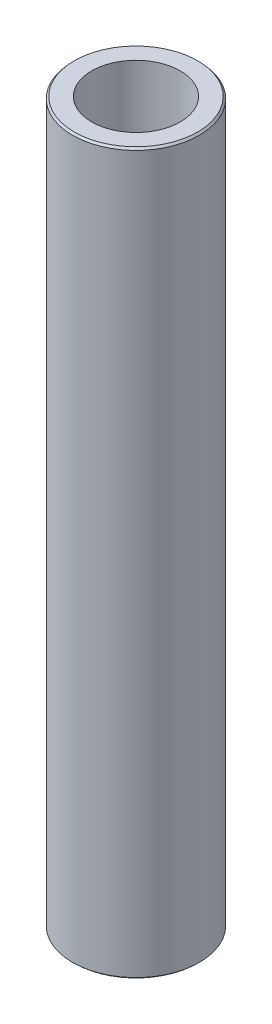
SolidWorks part; units mm, degrees
ref_plane "Front Plane" through (0, 0, 0) normal (0, 0, 1) x (1, 0, 0)
ref_plane "Top Plane" through (0, 0, 0) normal (0, 1, 0) x (1, 0, 0)
ref_plane "Right Plane" through (0, 0, 0) normal (1, 0, 0) x (0, 0, -1)
sketch "Sketch1" plane through (0, 0, 0) normal (0, 1, 0) x (1, 0, 0)
  circle A0 centre (0, 0) radius 45
  dimension "SHAFT_OD" = 90
extrude "Boss-Extrude1" add sketch "Sketch1" along normal blind 510.4486
sketch "Sketch2" plane through (0, 0, 0) normal (0, 1, 0) x (1, 0, 0)
  circle A0 centre (0, 0) radius 31.3927
  dimension "BORE_D" = 62.7854
extrude "Cut-Extrude1" cut sketch "Sketch2" along normal through all
chamfer "Chamfer1" distance 1.3699 angle 42.287 2 edges at (0, 510.4486, 45) (0, 0, 45) first distance on face at (0, 510.4486, 45) first distance on face at (0, 0, 31.3927)
